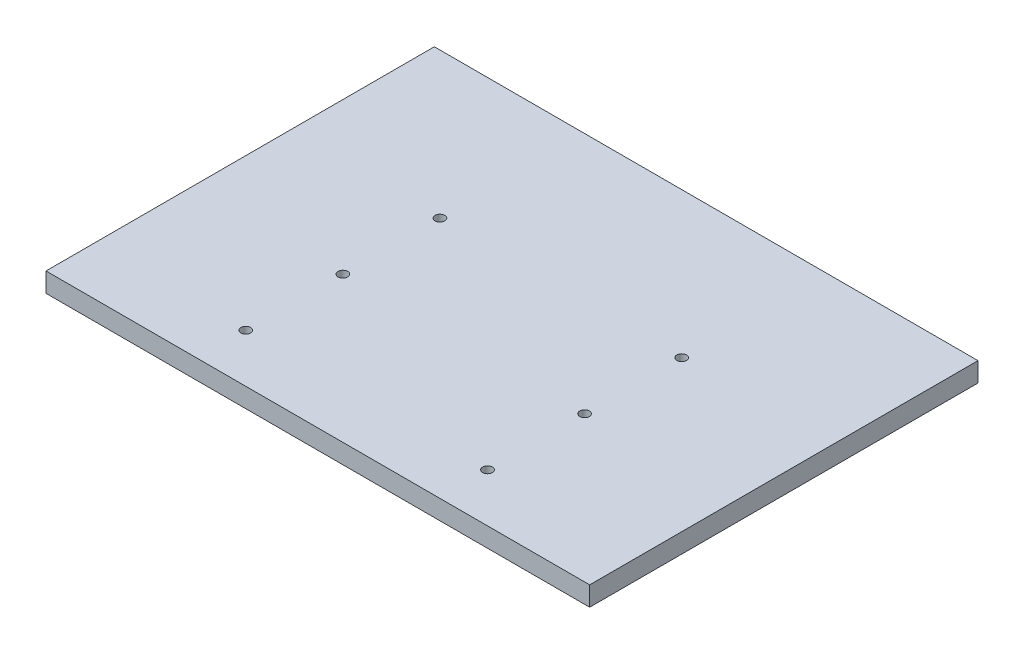
SolidWorks part; units mm, degrees
material "Alloy Steel (SS)"
ref_plane "Front Plane" through (0, 0, 0) normal (0, 0, 1) x (1, 0, 0)
ref_plane "Top Plane" through (0, 0, 0) normal (0, 1, 0) x (1, 0, 0)
ref_plane "Right Plane" through (0, 0, 0) normal (1, 0, 0) x (0, 0, -1)
sketch "Sketch1" plane through (0, 0, 0) normal (0, 1, 0) x (1, 0, 0)
  line L1 (-175.7216, 120.2519) -> (535.4784, 120.2519)
  line L2 (-175.7216, 120.2519) -> (-175.7216, -387.7481)
  line L3 (-175.7216, -387.7481) -> (535.4784, -387.7481)
  line L4 (535.4784, 120.2519) -> (535.4784, -387.7481)
  dimension "D1" = 711.2
  dimension "D2" = 508
extrude "Boss-Extrude1" add sketch "Sketch1" along normal blind 25.4
sketch "Sketch3" plane through (0, 25.4, 0) normal (0, 1, 0) x (1, 0, 0)
  line L0 (-175.7216, -387.7481) -> (535.4784, -387.7481) construction
  line L1 (-175.7216, 120.2519) -> (-175.7216, -387.7481) construction
  circle A0 centre (22.119, -324.2481) radius 6.35
  circle A1 centre (338.349, -324.2481) radius 6.35
  circle A2 centre (22.119, -197.2481) radius 6.35
  circle A3 centre (22.119, -70.2481) radius 6.35
  circle A4 centre (338.349, -70.2481) radius 6.35
  circle A5 centre (338.349, -197.2481) radius 6.35
  point P16 (0, 0)
  point P17 (0, 0)
  dimension "D1" = 12.7
  dimension "D4" = 12.7
  dimension "D5" = 12.7
  dimension "D6" = 12.7
  dimension "D7" = 12.7
  dimension "D8" = 12.7
  dimension "D2" = 63.5
  dimension "D3" = 197.8406
  dimension "D9" = 254
  dimension "D10" = 127
  dimension "D11" = 127
  dimension "D12" = 316.23
extrude "Cut-Extrude1" cut sketch "Sketch3" against normal through all
